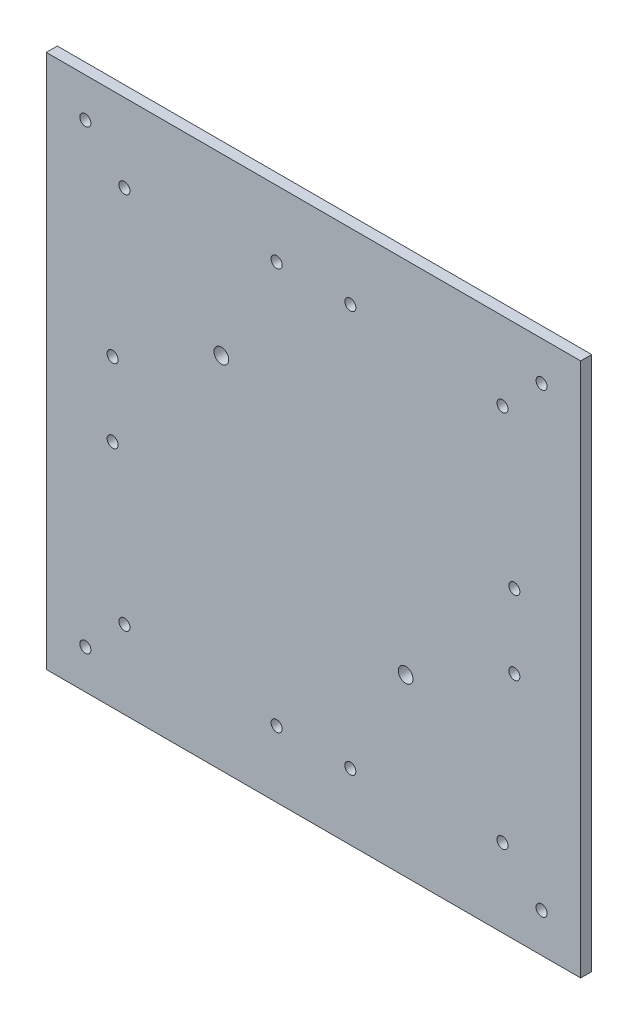
SolidWorks part; units mm, degrees
ref_plane "前视基准面" through (0, 0, 0) normal (0, 0, 1) x (1, 0, 0)
ref_plane "上视基准面" through (0, 0, 0) normal (0, 1, 0) x (1, 0, 0)
ref_plane "右视基准面" through (0, 0, 0) normal (1, 0, 0) x (0, 0, -1)
sketch "草图1" plane through (0, 0, 0) normal (0, 0, 1) x (1, 0, 0)
  line L1 (72.5, -72.5) -> (-72.5, -72.5)
  line L2 (72.5, -72.5) -> (72.5, 72.5)
  line L3 (72.5, 72.5) -> (-72.5, 72.5)
  line L4 (-72.5, -72.5) -> (-72.5, 72.5)
  line L5 (72.5, -72.5) -> (-72.5, 72.5) construction
  line L6 (72.5, 72.5) -> (-72.5, -72.5) construction
  point P0 (0, 0)
  dimension "D1" = 145
  dimension "D2" = 145
extrude "凸台-拉伸1" add sketch "草图1" along normal blind 3
sketch "草图2" plane through (0, 0, 3) normal (0, 0, 1) x (1, 0, 0)
  line L0 (-72.5, 0) -> (-54.5, 0) construction
  line L1 (-72.5, 72.5) -> (-72.5, -72.5) construction
  line L2 (-54.5, 0) -> (-54.5, -10) construction
  circle A0 centre (-54.5, -10) radius 1.5
  circle A1 centre (-54.5, 10) radius 1.5
  circle A2 centre (10, 54.5) radius 1.5
  circle A3 centre (-10, 54.5) radius 1.5
  circle A4 centre (54.5, -10) radius 1.5
  circle A5 centre (54.5, 10) radius 1.5
  circle A6 centre (-10, -54.5) radius 1.5
  circle A7 centre (10, -54.5) radius 1.5
  point P24 (0, 0)
  dimension "D3" = 3
  dimension "D1" = 18
  dimension "D2" = 10
  dimension "D4" = 4
extrude "切除-拉伸2" cut sketch "草图2" against normal blind 3
sketch "草图3" plane through (0, 0, 3) normal (0, 0, 1) x (1, 0, 0)
  line L1 (-72.5, 72.5) -> (-42.5, 72.5)
  line L2 (-72.5, 72.5) -> (-72.5, 42.5)
  line L3 (-72.5, 42.5) -> (-42.5, 42.5)
  line L4 (-42.5, 72.5) -> (-42.5, 42.5)
  line L6 (-72.5, 72.5) -> (-42.5, 42.5) construction
  circle A0 centre (-61.8934, 61.8934) radius 1.5
  circle A1 centre (-51.2868, 51.2868) radius 1.5
  circle A2 centre (61.8934, 61.8934) radius 1.5
  circle A3 centre (51.2868, 51.2868) radius 1.5
  circle A4 centre (61.8934, -61.8934) radius 1.5
  circle A5 centre (51.2868, -51.2868) radius 1.5
  circle A6 centre (-61.8934, -61.8934) radius 1.5
  circle A7 centre (-51.2868, -51.2868) radius 1.5
  point P24 (0, 0)
  dimension "D3" = 15
  dimension "D5" = 3
  dimension "D6" = 3
  dimension "D1" = 30
  dimension "D2" = 30
  dimension "D4" = 30
  dimension "D7" = 4
extrude "切除-拉伸3" cut sketch "草图3" against normal blind 3 contours A0 | A1 | A3 | A2 | A7 | A6 | A4 | A5
sketch "草图5" plane through (0, 0, 3) normal (0, 0, 1) x (1, 0, 0)
  line L1 (25, -25) -> (-25, -25) construction
  line L2 (25, -25) -> (25, 25) construction
  line L3 (25, 25) -> (-25, 25) construction
  line L4 (-25, -25) -> (-25, 25) construction
  line L5 (25, -25) -> (-25, 25) construction
  line L6 (25, 25) -> (-25, -25) construction
  circle A0 centre (25, -25) radius 2
  circle A1 centre (-25, 25) radius 2
  point P0 (0, 0)
  dimension "D3" = 4
  dimension "D4" = 4
  dimension "D1" = 50
  dimension "D2" = 50
extrude "切除-拉伸4" cut sketch "草图5" against normal blind 3
